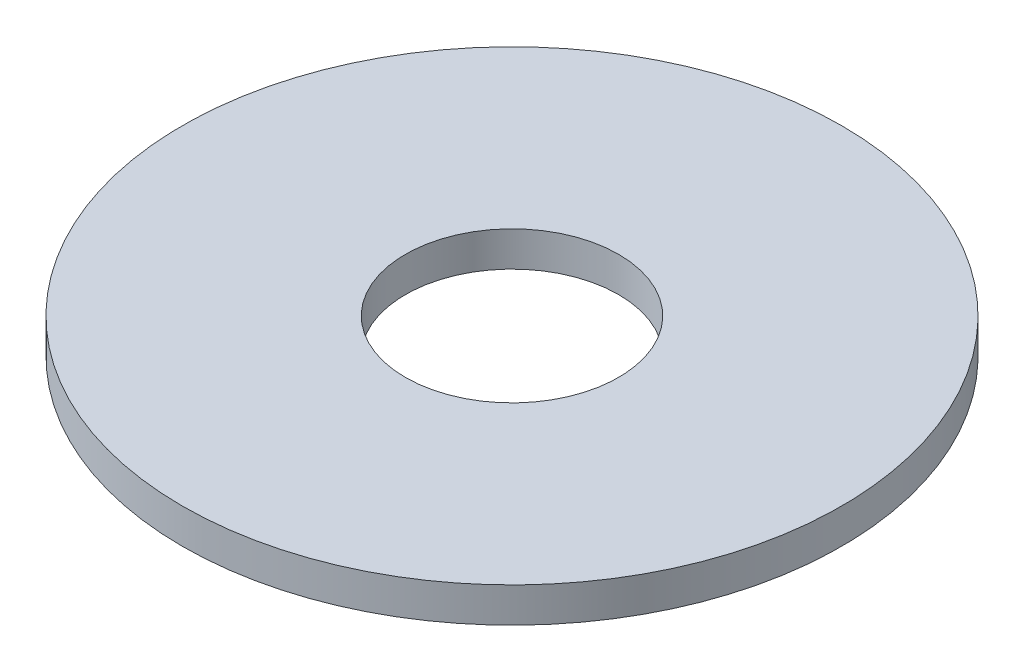
SolidWorks part; units mm, degrees
ref_plane "Front Plane" through (0, 0, 0) normal (0, 0, 1) x (1, 0, 0)
ref_plane "Top Plane" through (0, 0, 0) normal (0, 1, 0) x (1, 0, 0)
ref_plane "Right Plane" through (0, 0, 0) normal (1, 0, 0) x (0, 0, -1)
sketch "Sketch1" plane through (0, 0, 0) normal (0, 1, 0) x (1, 0, 0)
  circle A0 centre (0, 0) radius 85
  dimension "FLANGE_OD" = 170
extrude "Boss-Extrude1" add sketch "Sketch1" along normal blind 9
sketch "Sketch2" plane through (0, 0, 0) normal (0, 1, 0) x (1, 0, 0)
  circle A0 centre (0, 0) radius 27.5
  dimension "BORE_D" = 55
extrude "Cut-Extrude1" cut sketch "Sketch2" along normal through all
sketch "Sketch3" plane through (0, 9, 0) normal (0, 1, 0) x (1, 0, 0)
  circle A0 centre (0, 0) radius 23.2032 construction
  circle A1 centre (-23.2032, 0) radius 3.5058
  dimension "BOLT_D" = 7.0115
  dimension "BOLT_PCD" = 46.4064
extrude "Cut-Extrude2" cut sketch "Sketch3" against normal blind 6.7533 rebuild error yes
pattern_circular "CirPattern1" count 4 over 360 rebuild error yes
